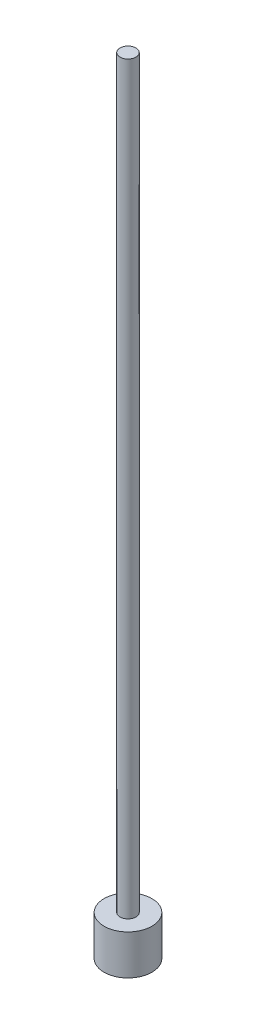
SolidWorks part; units mm, degrees
ref_plane "Front Plane" through (0, 0, 0) normal (0, 0, 1) x (1, 0, 0)
ref_plane "Top Plane" through (0, 0, 0) normal (0, 1, 0) x (1, 0, 0)
ref_plane "Right Plane" through (0, 0, 0) normal (1, 0, 0) x (0, 0, -1)
other "Configuration Table"
sketch "Sketch1" plane through (0, 0, 0) normal (0, 1, 0) x (1, 0, 0)
  circle A0 centre (0, 0) radius 30
extrude "Boss-Extrude1" add sketch "Sketch1" along normal blind 2800 separate body
sketch "Sketch2" plane through (0, 0, 0) normal (0, 1, 0) x (1, 0, 0)
  circle A0 centre (0, 0) radius 90
extrude "Boss-Extrude2" add sketch "Sketch2" against normal blind 150 flip side to cut separate body
